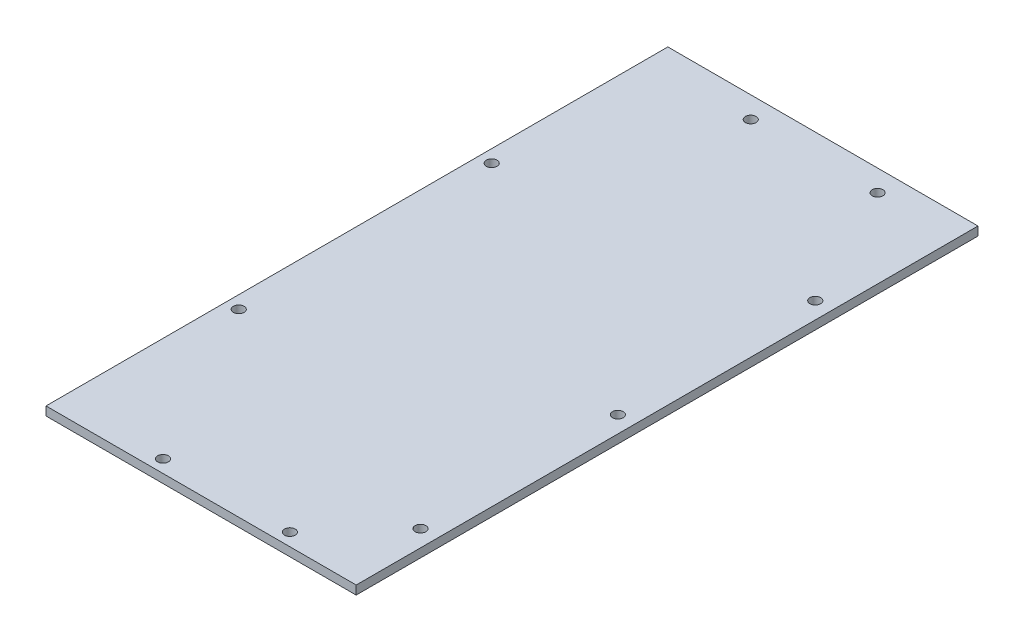
SolidWorks part; units mm, degrees
ref_plane "Front Plane" through (0, 0, 0) normal (0, 0, 1) x (1, 0, 0)
ref_plane "Top Plane" through (0, 0, 0) normal (0, 1, 0) x (1, 0, 0)
ref_plane "Right Plane" through (0, 0, 0) normal (1, 0, 0) x (0, 0, -1)
sketch "Sketch1" plane through (0, 0, 0) normal (0, 1, 0) x (1, 0, 0)
  line L1 (-55, 110.2663) -> (55, 110.2663)
  line L2 (-55, 110.2663) -> (-55, -110.2662)
  line L3 (-55, -110.2662) -> (55, -110.2662)
  line L4 (55, 110.2663) -> (55, -110.2662)
  line L5 (-55, 110.2663) -> (55, -110.2662) construction
  line L6 (-55, -110.2662) -> (55, 110.2663) construction
  point P0 (0, 0)
  dimension "D1" = 110
  dimension "D2" = 220.5325
extrude "Boss-Extrude1" add sketch "Sketch1" along normal blind 3.1
sketch "Sketch2" plane through (0, 3.1, 0) normal (0, 1, 0) x (1, 0, 0)
  point P0 (-17.9997, -105.7704)
  point P1 (27.0003, -105.7704)
  point P3 (-50.4997, -46.4113)
  point P5 (-50.4997, 43.3071)
  point P7 (-17.9997, 102.6663)
  point P9 (27.0003, 102.6663)
  point P11 (49.1, 58.45)
  point P13 (49.1, -11.55)
  point P15 (49.1, -81.55)
hole_wizard "#6 Clearance Hole1" positions "Sketch3" profile "Sketch4" hole size "#6" standard "ANSI Inch" end condition through all
sketch "Sketch3" plane through (0, 3.1, 0) normal (0, 1, 0) x (1, 0, 0)
  point P6 (49.1, 58.45)
  point P9 (49.1, -11.55)
  point P12 (49.1, -81.55)
  point P21 (-50.4997, -46.4113)
  point P24 (-50.4997, 43.3071)
  point P29 (0, 0)
  point P30 (0, 0)
  point P31 (0, 0)
  point P32 (0, 0)
sketch "Sketch4" plane through (49.1, 3.1, -58.45) normal (1, 0, 0) x (0, 0, 1)
  line L0 (0, 0) -> (0, 3.1)
  line L1 (0, 3.1) -> (1.8986, 3.1)
  line L2 (1.8986, 3.1) -> (1.8986, 0)
  line L5 (1.8986, 0) -> (0, 0)
  line L11 (0, -6.35) -> (0, 107.95) construction
  dimension "Thru Hole Dia." = 3.7973
  dimension "Thru Hole Depth" = 3.1
hole_wizard "#6 Clearance Hole3" positions "Sketch5" profile "Sketch6" hole size "#6" standard "ANSI Inch" end condition through all
sketch "Sketch5" plane through (0, 0, 0) normal (0, -1, 0) x (-1, 0, 0)
  point P0 (-27.0003, 102.6663)
  point P3 (17.9997, 102.6663)
  point P6 (-27.0003, -105.7704)
  point P9 (17.9997, -105.7704)
sketch "Sketch6" plane through (27.0003, 0, -102.6663) normal (1, 0, 0) x (0, 0, -1)
  line L0 (0, 0) -> (0, 3.1)
  line L1 (0, 3.1) -> (1.8986, 3.1)
  line L2 (1.8986, 3.1) -> (1.8986, 0)
  line L5 (1.8986, 0) -> (0, 0)
  line L11 (0, -6.35) -> (0, 107.95) construction
  dimension "Thru Hole Dia." = 3.7973
  dimension "Thru Hole Depth" = 3.1
